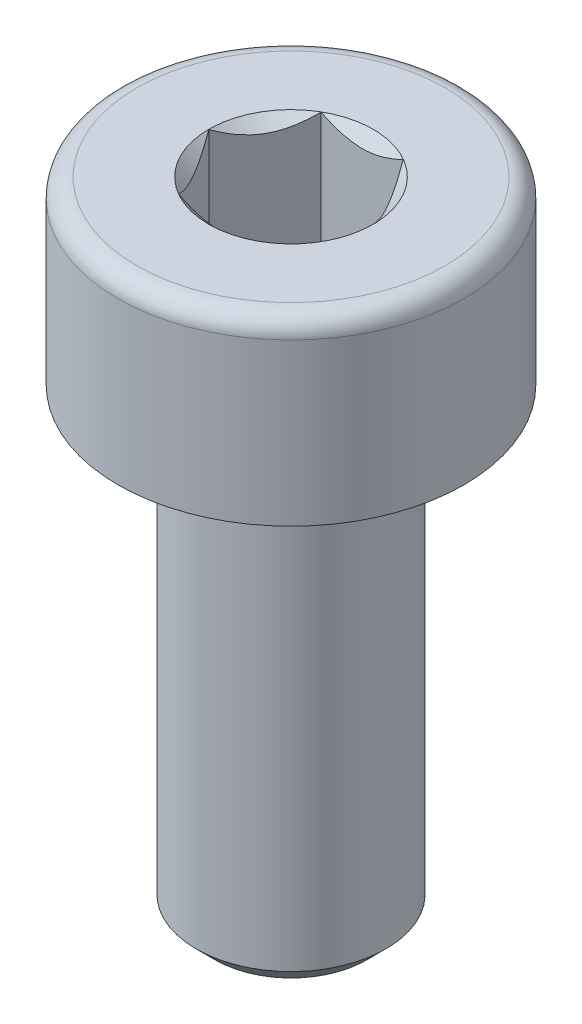
SolidWorks part; units mm, degrees
material "ASTM A36 Steel"
ref_plane "Front" through (0, 0, 0) normal (0, 0, 1) x (1, 0, 0)
ref_plane "Top" through (0, 0, 0) normal (0, 1, 0) x (1, 0, 0)
ref_plane "Right" through (0, 0, 0) normal (1, 0, 0) x (0, 0, -1)
sketch "Sketch1" plane through (0, 0, 0) normal (1, 0, 0) x (0, 0, -1)
  line L0 (0, 2.8377) -> (0, 0) construction
  line L1 (0, 0) -> (4.4824, 0) construction
  line L2 (0, -4.85) -> (0.8, -4.85)
  line L3 (0.8, -4.85) -> (1, -4.65)
  line L4 (1, -4.65) -> (1, -0.2)
  line L5 (1.2, 0) -> (1.825, 0)
  line L6 (1.825, 0) -> (1.825, 1.7)
  line L7 (1.625, 1.9) -> (0.8675, 1.9)
  line L8 (0, 0.1991) -> (0, -4.85)
  line L9 (0.75, 1.7825) -> (0.75, 0.9)
  line L10 (0.8675, 0.7) -> (0, 0.1991)
  line L11 (0.8675, 1.9) -> (0.75, 1.7825)
  line L12 (0.8675, 0.9) -> (0.8675, 0.7)
  line L13 (0.8675, 0.9) -> (0.75, 0.9)
  arc A0 (1, -0.2) -> (1.2, 0) centre (1.2, -0.2) cw
  arc A1 (1.825, 1.7) -> (1.625, 1.9) centre (1.625, 1.7) ccw
  dimension "D6" = 0.2
  dimension "D8" = 1.5
  dimension "D1" = 1.9
  dimension "D2" = 3.65
  dimension "D3" = 4.85
  dimension "D4" = 45
  dimension "D5" = 2
  dimension "D7" = 0.2
  dimension "D9" = 60
  dimension "D10" = 45
  dimension "D11" = 1.735
  dimension "D12" = 1
  dimension "D13" = 0.2
revolve "Revolve1" add sketch "Sketch1" angle 360 about L0
cosmetic thread "Cosmetic Thread1" parameters "D2"=1.548
sketch "Sketch2" plane through (0, 1.9, 0) normal (0, 1, 0) x (1, 0, 0)
  line L1 (0.433, -0.75) -> (0.866, 0)
  line L2 (0.866, 0) -> (0.433, 0.75)
  line L3 (0.433, 0.75) -> (-0.433, 0.75)
  line L4 (-0.433, 0.75) -> (-0.866, 0)
  line L5 (-0.866, 0) -> (-0.433, -0.75)
  line L6 (-0.433, -0.75) -> (0.433, -0.75)
  circle A0 centre (0, 0) radius 0.75 construction
  circle A1 centre (0, 0) radius 1.3095
  dimension "D1" = 1.5
extrude "Cut-Extrude1" cut sketch "Sketch2" against normal blind 1.1 contours L5 L6 L1 L2 L3 L4 region at (0, 1.9, 0)
extrude "Boss-Extrude1" add sketch "Sketch2<3>" against normal up to surface (0.4448 mm away) from offset 0.5 offset against normal yes
sketch "Sketch2<3>" plane through (0, 1.9, 0) normal (0, 1, 0) x (1, 0, 0) same geometry as "Sketch2"
